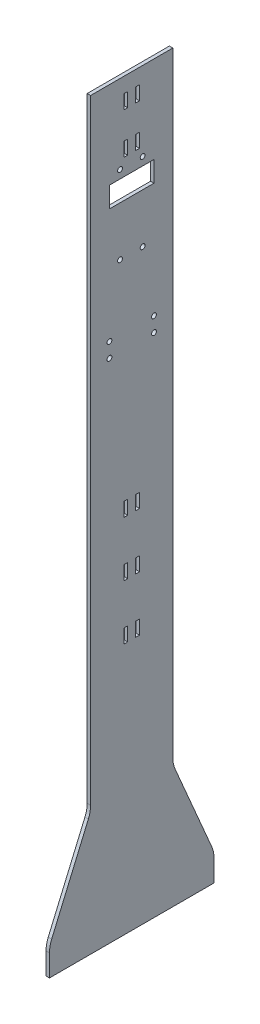
SolidWorks part; units mm, degrees
ref_plane "Front Plane" through (0, 0, 0) normal (0, 0, 1) x (1, 0, 0)
ref_plane "Top Plane" through (0, 0, 0) normal (0, 1, 0) x (1, 0, 0)
ref_plane "Right Plane" through (0, 0, 0) normal (1, 0, 0) x (0, 0, -1)
sketch "Sketch1" plane through (0, 0, 0) normal (1, 0, 0) x (0, 0, -1)
  line L1 (-38.1, 457.2) -> (38.1, 457.2)
  line L2 (-38.1, 457.2) -> (-38.1, -457.2)
  line L3 (-38.1, -457.2) -> (38.1, -457.2)
  line L4 (38.1, 457.2) -> (38.1, -457.2)
  line L5 (-38.1, 457.2) -> (38.1, -457.2) construction
  line L6 (-38.1, -457.2) -> (38.1, 457.2) construction
  point P0 (0, 0)
  dimension "D1" = 914.4
  dimension "D2" = 76.2
extrude "Boss-Extrude1" add sketch "Sketch1" along normal blind 3.175
sketch "Sketch2" plane through (3.175, 0, 0) normal (1, 0, 0) x (0, 0, -1)
  line L0 (-38.1, -457.2) -> (38.1, -457.2) construction
  line L1 (3.722, -204.5335) -> (7.278, -204.5335)
  line L2 (3.722, -204.5335) -> (3.722, -217.4875)
  line L3 (3.722, -217.4875) -> (7.278, -217.4875)
  line L4 (7.278, -204.5335) -> (7.278, -217.4875)
  line L5 (3.722, -204.5335) -> (7.278, -217.4875) construction
  line L6 (3.722, -217.4875) -> (7.278, -204.5335) construction
  point P0 (5.5, -211.0105)
  dimension "D1" = 3.556
  dimension "D2" = 12.954
  dimension "D3" = 239.7125
  dimension "D4" = 3.722
extrude "Cut-Extrude1" cut sketch "Sketch2" against normal through all
mirror "Mirror1" about plane through (0, 0, 0) normal (0, 0, 1) of "Cut-Extrude1"
pattern_linear "LPattern1" count 2 spacing 50.8 along (0, 1, 0) count 2 spacing 50.8 along (0, -1, 0) of "Mirror1"
sketch "Sketch3" plane through (3.175, 0, 0) normal (1, 0, 0) x (0, 0, -1)
  line L0 (7.278, -166.6875) -> (7.278, -153.7335) construction
  line L1 (3.722, 135.1915) -> (7.278, 135.1915)
  line L2 (3.722, 135.1915) -> (3.722, 122.2375)
  line L3 (3.722, 122.2375) -> (7.278, 122.2375)
  line L4 (7.278, 135.1915) -> (7.278, 122.2375)
  line L5 (3.722, 135.1915) -> (7.278, 122.2375) construction
  line L6 (3.722, 122.2375) -> (7.278, 135.1915) construction
  line L7 (7.278, -153.7335) -> (3.722, -153.7335) construction
  line L8 (3.722, -153.7335) -> (3.722, -166.6875) construction
  line L9 (0, 0) -> (0, 52.1648) construction
  line L10 (-3.722, 122.2375) -> (-7.278, 135.1915) construction
  line L11 (-3.722, 135.1915) -> (-7.278, 122.2375) construction
  line L12 (-7.278, 135.1915) -> (-7.278, 122.2375)
  line L13 (-3.722, 122.2375) -> (-7.278, 122.2375)
  line L14 (-3.722, 135.1915) -> (-3.722, 122.2375)
  line L15 (-3.722, 135.1915) -> (-7.278, 135.1915)
  point P0 (5.5, 128.7145)
  point P18 (-5.5, 128.7145)
  dimension "D1" = 275.971
extrude "Cut-Extrude2" cut sketch "Sketch3" against normal through all
pattern_linear "LPattern2" count 2 spacing 38.1 along (0, 1, 0) of "Cut-Extrude2"
sketch "Sketch4" plane through (3.175, 0, 0) normal (1, 0, 0) x (0, 0, -1)
  line L0 (0, -457.2) -> (0, 187.325) construction
  line L1 (-38.1, -457.2) -> (38.1, -457.2) construction
  line L2 (0, 187.325) -> (-38.1, 187.325)
  line L3 (-38.1, 457.2) -> (-38.1, -457.2) construction
  line L4 (-38.1, 187.325) -> (38.1, 187.325)
  line L5 (38.1, -457.2) -> (38.1, 457.2) construction
  line M30 (38.1, -457.2) -> (38.1, 457.2)
  line M31 (38.1, 457.2) -> (-38.1, 457.2)
  line M32 (-38.1, 457.2) -> (-38.1, -457.2)
  dimension "D1" = 644.525
extrude "Cut-Extrude3" cut sketch "Sketch4" against normal through all contours L2 L4 M30 M31 M32 region at (3.175, 322.2625, 0)
sketch "Sketch5" plane through (3.175, 0, 0) normal (1, 0, 0) x (0, 0, -1)
  line L0 (-38.1, -457.2) -> (-38.1, -501.65)
  line L1 (-38.1, -501.65) -> (38.1, -501.65)
  line L2 (38.1, -501.65) -> (38.1, -457.2)
  line L7 (38.1, -457.2) -> (38.1, 187.325)
  line L8 (38.1, 187.325) -> (-38.1, 187.325)
  line L9 (-38.1, 187.325) -> (-38.1, -457.2)
  line L10 (-38.1, -457.2) -> (38.1, -457.2)
  line L14 (-38.1, -457.2) -> (38.1, -457.2)
  dimension "D1" = 44.45
  dimension "D2" = 0
extrude "Boss-Extrude2" add sketch "Sketch5" against normal up to surface (3.175 mm away) up to face at (0, -160.2105, 5.5)
sketch "Sketch6" plane through (3.175, 0, 0) normal (1, 0, 0) x (0, 0, -1)
  line L1 (-20.6375, 106.6318) -> (20.6375, 106.6318)
  line L2 (-20.6375, 106.6318) -> (-20.6375, 87.5818)
  line L4 (20.6375, 106.6318) -> (20.6375, 87.5818)
  line L5 (0, 187.325) -> (0, 38.8722) construction
  line L6 (38.1, 187.325) -> (-38.1, 187.325) construction
  line L7 (-20.6375, 87.5818) -> (20.6375, 87.5818)
  line L8 (-20.9831, 119.3318) -> (20.2919, 119.3318) construction
  point P6 (0, 106.6318)
  dimension "D1" = 19.05
  dimension "D2" = 41.275
  dimension "D3" = 12.7
extrude "Cut-Extrude4" cut sketch "Sketch6" against normal through all contours L7 L4 L1 L2
sketch "Sketch7" plane through (3.175, 0, 0) normal (1, 0, 0) x (0, 0, -1)
  line L0 (-76.2, -501.65) -> (76.2, -501.65)
  line L1 (76.2, -501.65) -> (76.2, -476.25)
  line L2 (76.2, -476.25) -> (38.1, -387.35)
  line L3 (38.1, -501.65) -> (38.1, 187.325) construction
  line L4 (38.1, -387.35) -> (-38.1, -387.35)
  line L5 (-38.1, 187.325) -> (-38.1, -501.65) construction
  line L6 (-38.1, -387.35) -> (-76.2, -476.25)
  line L7 (-76.2, -476.25) -> (-76.2, -501.65)
  line L8 (-38.1, -501.65) -> (38.1, -501.65) construction
  dimension "D1" = 152.4
  dimension "D2" = 38.1
  dimension "D3" = 25.4
  dimension "D4" = 114.3
extrude "Boss-Extrude3" add sketch "Sketch7" against normal blind 3.175
fillet "Fillet1" radius 25.4 4 edges at (1.5875, -476.25, 76.2) (1.5875, -387.35, 38.1) (1.5875, -476.25, -76.2) (1.5875, -387.35, -38.1)
hole_wizard "#8 Clearance Hole1" positions "Sketch8" profile "Sketch9" hole size "#8" standard "ANSI Inch" end condition through all
sketch "Sketch8" plane through (3.175, 0, 0) normal (1, 0, 0) x (0, 0, -1)
  point P0 (10.1319, 41.8618)
  point P3 (-10.8231, 41.8618)
  point P6 (20.6375, -18.8258)
  point P9 (-20.6375, -18.8258)
  point P12 (20.6375, -32.3008)
  point P15 (-20.6375, -32.3008)
  point P19 (10.1319, 114.2518)
  point P22 (-10.8231, 114.2518)
sketch "Sketch9" plane through (3.175, 41.8618, -10.1319) normal (0, 1, 0) x (0, 0, -1)
  line L0 (0, 0) -> (0, 3.175)
  line L1 (0, 3.175) -> (2.2479, 3.175)
  line L2 (2.2479, 3.175) -> (2.2479, 0)
  line L5 (2.2479, 0) -> (0, 0)
  line L11 (0, -6.35) -> (0, 107.95) construction
  dimension "Thru Hole Dia." = 4.4958
  dimension "Thru Hole Depth" = 3.175
